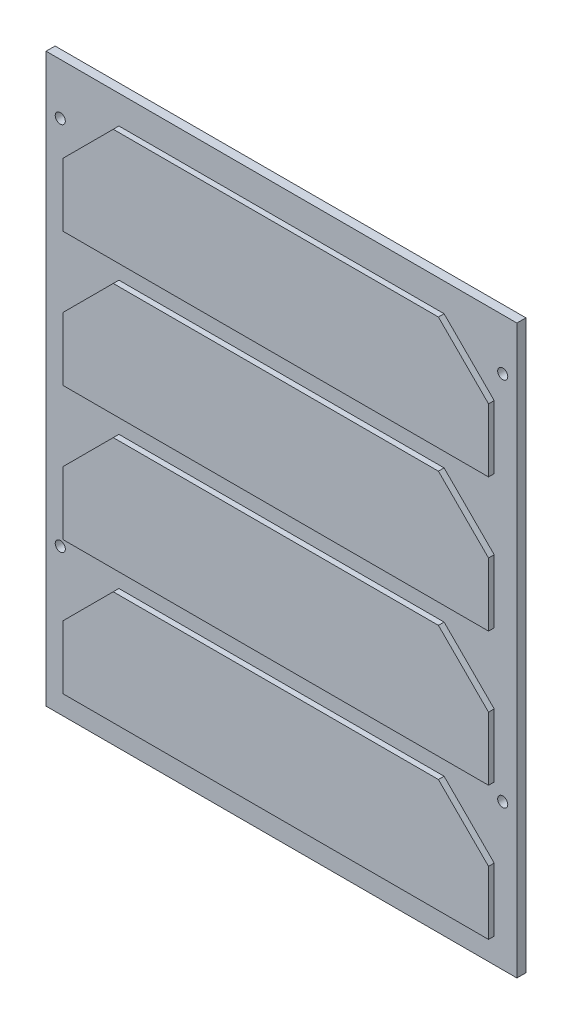
SolidWorks part; units mm, degrees
ref_plane "Front Plane" through (0, 0, 0) normal (0, 0, 1) x (1, 0, 0)
ref_plane "Top Plane" through (0, 0, 0) normal (0, 1, 0) x (1, 0, 0)
ref_plane "Right Plane" through (0, 0, 0) normal (1, 0, 0) x (0, 0, -1)
sketch "Sketch1" plane through (0, 0, 0) normal (0, 0, 1) x (1, 0, 0)
  line L1 (-41.5, -50) -> (41.5, -50)
  line L2 (-41.5, -50) -> (-41.5, 50)
  line L3 (-41.5, 50) -> (41.5, 50)
  line L4 (41.5, -50) -> (41.5, 50)
  line L5 (-41.5, -50) -> (41.5, 50) construction
  line L6 (-41.5, 50) -> (41.5, -50) construction
  point P0 (0, 0)
  dimension "D1" = 83
  dimension "D2" = 100
extrude "Boss-Extrude1" add sketch "Sketch1" along normal blind 1.5875
sketch "Sketch2" plane through (0, 0, 1.5875) normal (0, 0, 1) x (1, 0, 0)
  line L0 (-28.6612, 45) -> (28.6612, 45)
  line L1 (28.6612, 45) -> (37.5, 36.1612)
  line L2 (37.5, 36.1612) -> (37.5, 25)
  line L3 (37.5, 25) -> (-37.5, 25)
  line L4 (-37.5, 25) -> (-37.5, 36.1612)
  line L5 (-37.5, 36.1612) -> (-28.6612, 45)
  line L6 (0, 0) -> (0, 50) construction
  line L7 (41.5, 50) -> (-41.5, 50) construction
  line L8 (-28.6612, 21.4624) -> (28.6612, 21.4624)
  line L9 (28.6612, 21.4624) -> (37.5, 12.6236)
  line L10 (37.5, 12.6236) -> (37.5, 1.4624)
  line L11 (37.5, 1.4624) -> (-37.5, 1.4624)
  line L12 (-37.5, 1.4624) -> (-37.5, 12.6236)
  line L13 (-37.5, 12.6236) -> (-28.6612, 21.4624)
  line L14 (-28.6612, -2.0751) -> (28.6612, -2.0751)
  line L15 (28.6612, -2.0751) -> (37.5, -10.914)
  line L16 (37.5, -10.914) -> (37.5, -22.0751)
  line L17 (37.5, -22.0751) -> (-37.5, -22.0751)
  line L18 (-37.5, -22.0751) -> (-37.5, -10.914)
  line L19 (-37.5, -10.914) -> (-28.6612, -2.0751)
  line L20 (-28.6612, -25.6127) -> (28.6612, -25.6127)
  line L21 (28.6612, -25.6127) -> (37.5, -34.4515)
  line L22 (37.5, -34.4515) -> (37.5, -45.6127)
  line L23 (37.5, -45.6127) -> (-37.5, -45.6127)
  line L24 (-37.5, -45.6127) -> (-37.5, -34.4515)
  line L25 (-37.5, -34.4515) -> (-28.6612, -25.6127)
  dimension "D1" = 75
  dimension "D3" = 45
  dimension "D4" = 12.5
  dimension "D5" = 5
  dimension "D6" = 4
extrude "Boss-Extrude2" add sketch "Sketch2" along normal blind 1
hole_wizard "#0 Clearance Hole1" positions "Sketch4" profile "Sketch3" hole size "#0" standard "ANSI Inch"
sketch "Sketch4" plane through (0, 0, 1.5875) normal (0, 0, 1) x (1, 0, 0)
  line L1 (-41.5, 50) -> (-41.5, -50) construction
  line L2 (41.5, -50) -> (41.5, 50) construction
  line L6 (-39, 41) -> (-39, -24.3333) construction
  line L7 (-39, -24.3333) -> (-39, -89.6667) construction
  line L8 (-39, -89.6667) -> (-39, -155) construction
  line L10 (41.5, 50) -> (-41.5, 50) construction
  point P0 (-39, 41)
  point P2 (39, 41)
  point P4 (39, -24.3333)
  point P6 (39, -89.6667)
  point P8 (39, -155)
  point P10 (-39, -155)
  point P12 (-39, -89.6667)
  point P14 (-39, -24.3333)
  dimension "D1" = 196
  dimension "D2" = 2.5
  dimension "D3" = 2.5
  dimension "D4" = 9
sketch "Sketch3" plane through (-39, 41, 1.5875) normal (1, 0, 0) x (0, -1, 0)
  line L0 (0, 0) -> (0, 3.7092)
  line L1 (0, 3.7092) -> (0.889, 3.175)
  line L2 (0.889, 3.175) -> (0.889, 0)
  line L5 (0.889, 0) -> (0, 0)
  line L10 (0, 3.7092) -> (-0.889, 3.175) construction
  line L11 (0, -6.35) -> (0, 107.95) construction
  dimension "Hole Dia." = 1.778
  dimension "Hole Depth" = 3.175
  dimension "Drill Angle" = 118
